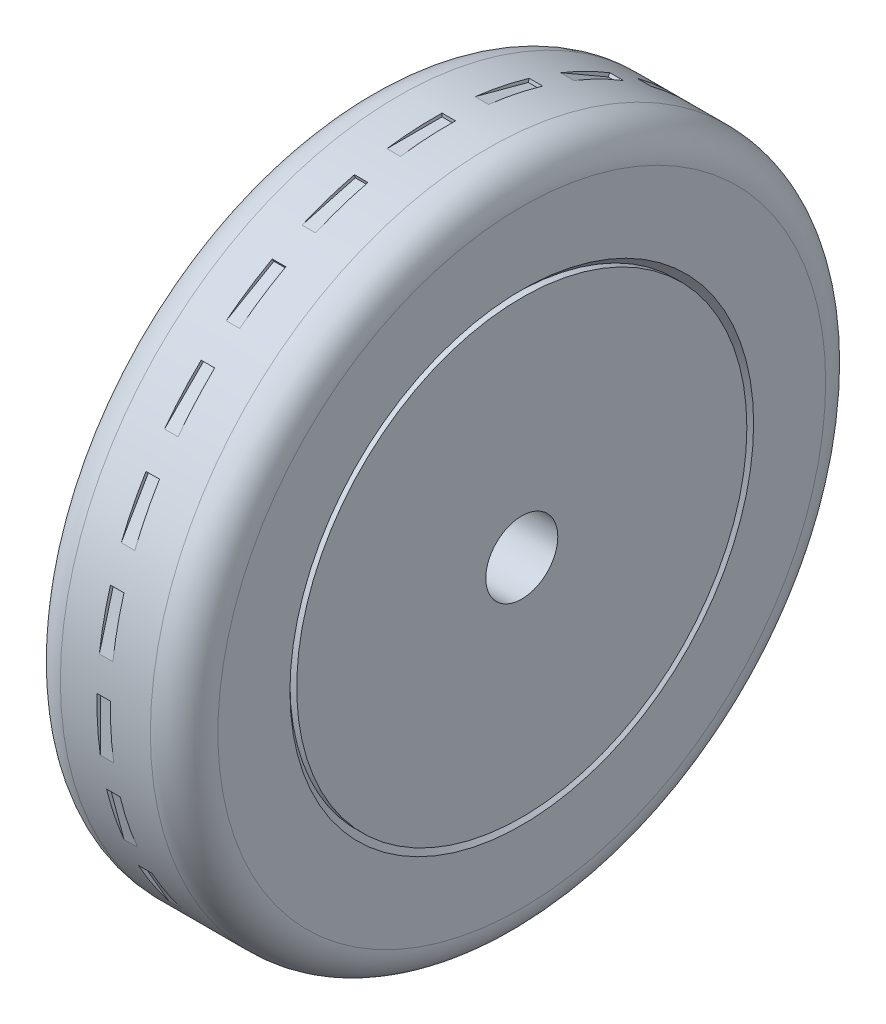
SolidWorks part; units mm, degrees
ref_plane "Front Plane" through (0, 0, 0) normal (0, 0, 1) x (1, 0, 0)
ref_plane "Top Plane" through (0, 0, 0) normal (0, 1, 0) x (1, 0, 0)
ref_plane "Right Plane" through (0, 0, 0) normal (1, 0, 0) x (0, 0, -1)
sketch "Sketch1" plane through (0, 0, 0) normal (0, 0, 1) x (1, 0, 0)
  line L0 (0, 60.35) -> (0, 0) construction
  line L1 (0, 0) -> (-57.936, 0) construction
  line L2 (-17.5, 50) -> (-17.5, 67.5)
  line L3 (-10, 75) -> (10, 75)
  line L4 (17.5, 67.5) -> (17.5, 50)
  line L5 (-14.5, 50) -> (-14.5, 67.5)
  line L6 (-10, 72) -> (10, 72)
  line L7 (14.5, 67.5) -> (14.5, 50)
  line L8 (-17.5, 50) -> (-14.5, 50)
  line L9 (14.5, 50) -> (17.5, 50)
  arc A0 (10, 75) -> (17.5, 67.5) centre (10, 67.5) cw
  arc A1 (-17.5, 67.5) -> (-10, 75) centre (-10, 67.5) cw
  arc A2 (-14.5, 67.5) -> (-10, 72) centre (-10, 67.5) cw
  arc A3 (10, 72) -> (14.5, 67.5) centre (10, 67.5) cw
  point P10 (17.5, 75)
  point P13 (-17.5, 75)
  dimension "D3" = 7.5
  dimension "D1" = 50
  dimension "D2" = 75
  dimension "D4" = 35
  dimension "D5" = 3
revolve "Revolve1" add sketch "Sketch1" angle 360 about L1
chamfer "Chamfer1" distance 1.5 angle 45 4 edges at (14.5, 0, -50) (17.5, 0, -50) (-17.5, 0, -50) (-14.5, 0, -50)
ref_plane "Plane1" through (0, 75, 0) normal (0, 1, 0) x (1, 0, 0)
sketch "Sketch3" plane through (0, 75, 0) normal (0, 1, 0) x (1, 0, 0)
  line L1 (-1.8732, 1.6631) -> (1.1268, 1.6631)
  line L2 (-1.8732, 1.6631) -> (-1.8732, -18.3369)
  line L3 (-1.8732, -18.3369) -> (1.1268, -18.3369)
  line L4 (1.1268, 1.6631) -> (1.1268, -18.3369)
extrude "Cut-Extrude3" cut sketch "Sketch3" against normal mid plane 1.5
pattern_circular "CirPattern2" count 24 every 15 about axis through (17.5, 0, 0) along (1, 0, 0) of "Cut-Extrude3"
ref_plane "Plane2" through (17.5, 0, 0) normal (1, 0, 0) x (0, 0, -1)
sketch "Sketch4" plane through (17.5, 0, 0) normal (1, 0, 0) x (0, 0, -1)
  circle A0 centre (0, 0) radius 50
  circle A1 centre (0, 0) radius 8
  dimension "D1" = 100
  dimension "D2" = 16
extrude "Boss-Extrude1" add sketch "Sketch4" against normal blind 34 separate body
